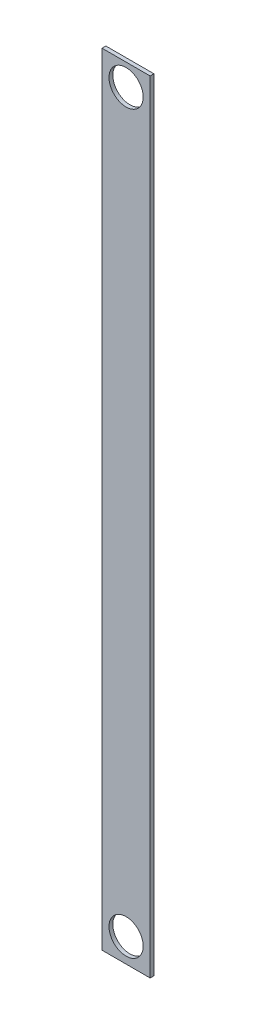
SolidWorks part; units mm, degrees
ref_plane "Front Plane" through (0, 0, 0) normal (0, 0, 1) x (1, 0, 0)
ref_plane "Top Plane" through (0, 0, 0) normal (0, 1, 0) x (1, 0, 0)
ref_plane "Right Plane" through (0, 0, 0) normal (1, 0, 0) x (0, 0, -1)
sketch "Sketch1" plane through (0, 0, 0) normal (0, 0, 1) x (1, 0, 0)
  line L1 (0, 0) -> (40, 0)
  line L2 (0, 0) -> (0, -650)
  line L3 (0, -650) -> (40, -650)
  line L4 (40, 0) -> (40, -650)
  dimension "D1" = 650
  dimension "D2" = 40
extrude "Boss-Extrude1" add sketch "Sketch1" along normal blind 3.175
sketch "Sketch2" plane through (0, 0, 3.175) normal (0, 0, 1) x (1, 0, 0)
  line L0 (40, 0) -> (0, 0) construction
  line L1 (20, 0) -> (20, -650) construction
  line L2 (0, -650) -> (40, -650) construction
  line L3 (0, -650) -> (40, -650) construction
  circle A0 centre (20, -18.1414) radius 14.224
  circle A1 centre (20, -630) radius 14.224
  point P9 (20, -650)
  dimension "D1" = 28.448
  dimension "D2" = 28.448
  dimension "D3" = 20
extrude "Cut-Extrude1" cut sketch "Sketch2" against normal through all
